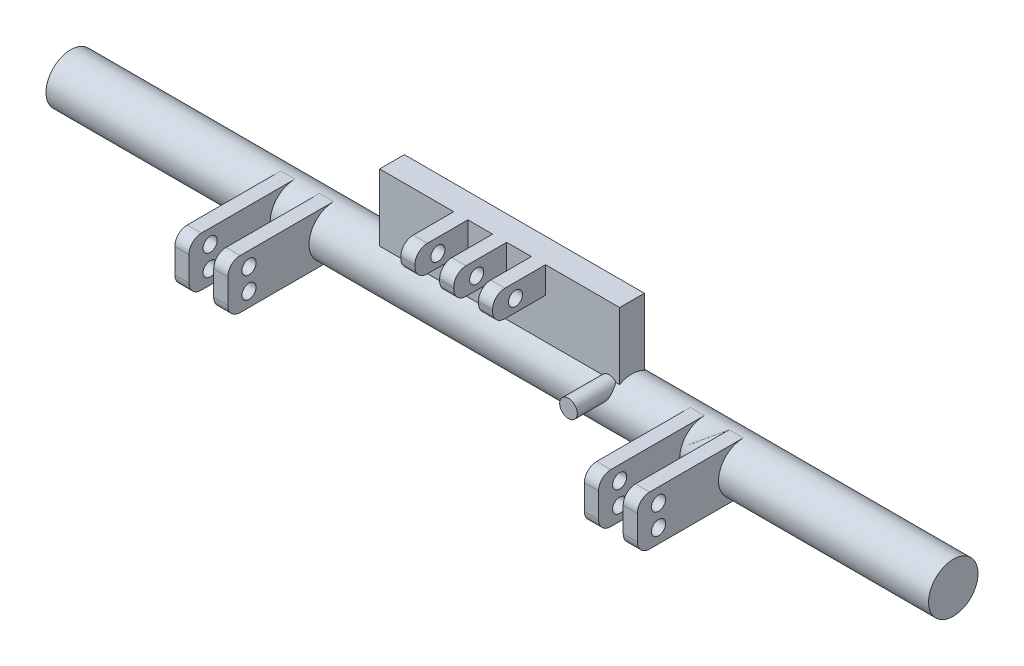
SolidWorks part; units mm, degrees
ref_plane "Front Plane" through (0, 0, 0) normal (0, 0, 1) x (1, 0, 0)
ref_plane "Top Plane" through (0, 0, 0) normal (0, 1, 0) x (1, 0, 0)
ref_plane "Right Plane" through (0, 0, 0) normal (1, 0, 0) x (0, 0, -1)
sketch "Sketch1" plane through (0, 0, 0) normal (0, 0, 1) x (1, 0, 0)
  line L0 (-125, 0) -> (125, 0)
  line L2 (-125, 7.5) -> (125, 7.5)
  line L3 (-125, 7.5) -> (-125, -7.5)
  line L4 (-125, -7.5) -> (125, -7.5)
  line L5 (125, 7.5) -> (125, -7.5)
  line L6 (-125, 7.5) -> (125, -7.5) construction
  line L7 (-125, -7.5) -> (125, 7.5) construction
  point P2 (0, 0)
  point P8 (0, 0)
  dimension "D1" = 250
  dimension "D2" = 15
revolve "Revolve-Thin1" add sketch "Sketch1" angle 360 about L0 wall 7
sketch "Sketch2" plane through (0, 0, 0) normal (0, 1, 0) x (1, 0, 0)
  line L1 (-34, -3.5) -> (34, -3.5)
  line L2 (-34, -3.5) -> (-34, 3.5)
  line L3 (-34, 3.5) -> (34, 3.5)
  line L4 (34, -3.5) -> (34, 3.5)
  line L5 (-34, -3.5) -> (34, 3.5) construction
  line L6 (-34, 3.5) -> (34, -3.5) construction
  point P0 (0, 0)
extrude "Boss-Extrude1" add sketch "Sketch2" along normal blind 25
sketch "Sketch3" plane through (0, 0, 3.5) normal (0, 0, 1) x (1, 0, 0)
  line L1 (-13, 25) -> (-9, 25)
  line L2 (-13, 25) -> (-13, 17.5)
  line L3 (-13, 17.5) -> (-9, 17.5)
  line L4 (-9, 25) -> (-9, 17.5)
  line L5 (-2, 25) -> (2, 25)
  line L6 (-2, 25) -> (-2, 17.5)
  line L7 (-2, 17.5) -> (2, 17.5)
  line L8 (2, 25) -> (2, 17.5)
  line L13 (9, 25) -> (13, 25)
  line L14 (9, 25) -> (9, 17.5)
  line L15 (9, 17.5) -> (13, 17.5)
  line L16 (13, 25) -> (13, 17.5)
  point P3 (0, 17.5)
  dimension "D1" = 17.5
  dimension "D2" = 7.5
  dimension "D3" = 7
  dimension "D4" = 4
  dimension "D5" = 4
  dimension "D6" = 7
  dimension "D7" = 4
  dimension "D8" = 7.5
extrude "Boss-Extrude2" add sketch "Sketch3" along normal blind 15
sketch "Sketch4" plane through (-13, 0, 0) normal (-1, 0, 0) x (0, 0, 1)
  line L0 (3.5, 25) -> (3.5, 6.0622) construction
  line L1 (18.5, 17.5) -> (3.5, 17.5) construction
  circle A0 centre (12, 21) radius 2
  dimension "D1" = 8.5
  dimension "D2" = 3.5
fillet "Fillet1" radius 3.5 6 edges at (-11, 17.5, 18.5) (-11, 25, 18.5) (11, 17.5, 18.5) (11, 25, 18.5) (0, 17.5, 18.5) (0, 25, 18.5)
sketch "Sketch5" plane through (0, 0, 0) normal (0, 0, 1) x (1, 0, 0)
  line L0 (-34, 7) -> (-125, 7) construction
  line L1 (-54.5, 7) -> (-50.5, 7)
  line L2 (-54.5, 7) -> (-54.5, -7)
  line L3 (-54.5, -7) -> (-50.5, -7)
  line L4 (-50.5, 7) -> (-50.5, -7)
  line L5 (-61.5, 7) -> (-65.5, 7)
  line L6 (-61.5, 7) -> (-61.5, -7)
  line L7 (-61.5, -7) -> (-65.5, -7)
  line L8 (-65.5, 7) -> (-65.5, -7)
  line L9 (-125, -7) -> (125, -7) construction
  line L10 (0, -14.025) -> (0, 14.025) construction
  line L11 (65.5, 7) -> (65.5, -7)
  line L12 (61.5, -7) -> (65.5, -7)
  line L13 (61.5, 7) -> (61.5, -7)
  line L14 (61.5, 7) -> (65.5, 7)
  line L15 (50.5, 7) -> (50.5, -7)
  line L16 (54.5, -7) -> (50.5, -7)
  line L17 (54.5, 7) -> (54.5, -7)
  line L18 (54.5, 7) -> (50.5, 7)
  line L19 (125, 7) -> (34, 7) construction
  line L20 (13, 17.5) -> (13, 25) construction
  circle A0 centre (31, 4.5) radius 2.5
  point P4 (-50.5, 0)
  point P28 (0, 0)
  point P29 (0, 0)
  point P30 (36.5095, 3.0099)
  dimension "D6" = 2.5
  dimension "D1" = 14
  dimension "D2" = 4
  dimension "D3" = 54.5
  dimension "D4" = 4
  dimension "D5" = 7
  dimension "D7" = 18
extrude "Boss-Extrude3" add sketch "Sketch5" along normal blind 30
fillet "Fillet2" radius 3.5 8 edges at (63.5, -7, 30) (52.5, -7, 30) (52.5, 7, 30) (63.5, 7, 30) (-52.5, -7, 30) (-63.5, -7, 30) (-52.5, 7, 30) (-63.5, 7, 30)
sketch "Sketch6" plane through (-65.5, 0, 0) normal (-1, 0, 0) x (0, 0, 1)
  line L0 (26.5, 7) -> (0, 7) construction
  line L1 (30, 3.5) -> (30, -3.5) construction
  line L2 (26.5, -7) -> (0, -7) construction
  circle A0 centre (24, 3) radius 2
  circle A1 centre (24, -3) radius 2
  dimension "D1" = 4
  dimension "D3" = 4
  dimension "D2" = 6
  dimension "D4" = 6
extrude "Cut-Extrude1" cut sketch "Sketch6" along normal through all and the other way through all
extrude "Cut-Extrude2" cut sketch "Sketch4" against normal through all
sketch "Sketch7" plane through (0, 0, 30) normal (0, 0, 1) x (1, 0, 0)
  circle A0 centre (31, 4.5) radius 2.5
extrude "Cut-Extrude3" cut sketch "Sketch7" against normal blind 15
